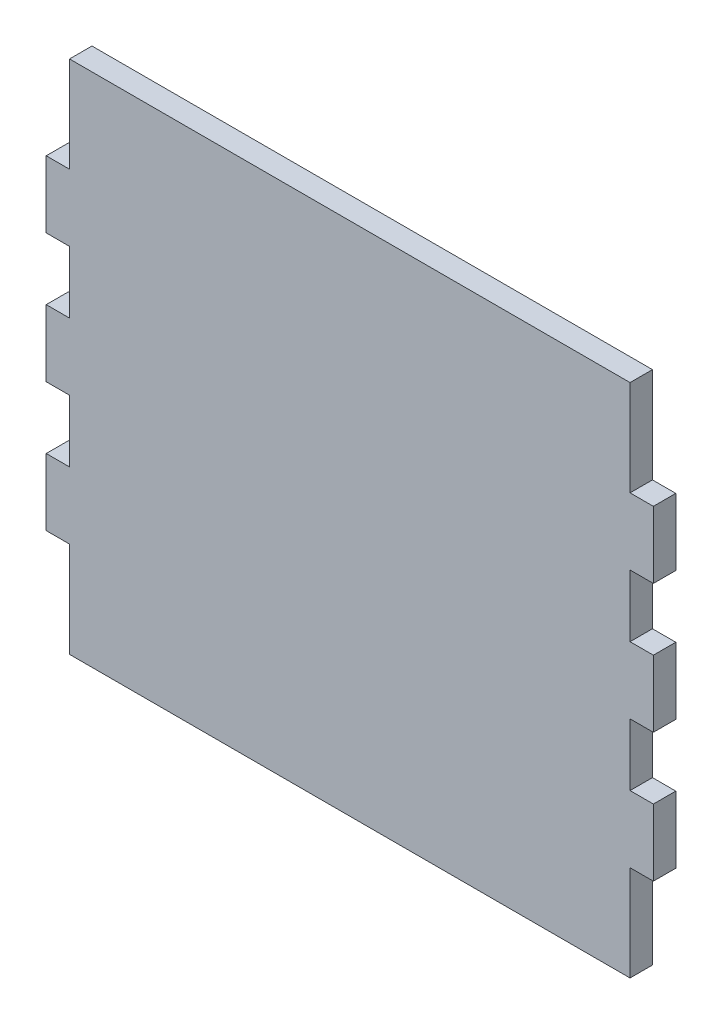
SolidWorks part; units mm, degrees
ref_plane "Front Plane" through (0, 0, 0) normal (0, 0, 1) x (1, 0, 0)
ref_plane "Top Plane" through (0, 0, 0) normal (0, 1, 0) x (1, 0, 0)
ref_plane "Right Plane" through (0, 0, 0) normal (1, 0, 0) x (0, 0, -1)
sketch "Sketch1" plane through (0, 0, 0) normal (0, 0, 1) x (1, 0, 0)
  line L0 (0, 0) -> (-85.979, 0) construction
  line L1 (79.375, 73.025) -> (-79.375, 73.025)
  line L2 (79.375, 73.025) -> (79.375, 45.974)
  line L3 (79.375, -73.025) -> (-79.375, -73.025)
  line L4 (-79.375, 73.025) -> (-79.375, 45.974)
  line L5 (79.375, 73.025) -> (-79.375, -73.025) construction
  line L6 (79.375, -73.025) -> (-79.375, 73.025) construction
  line L7 (-79.375, 9.4615) -> (-85.979, 9.4615)
  line L9 (-79.375, -9.4615) -> (-85.979, -9.4615)
  line L10 (-85.979, 9.4615) -> (-85.979, -9.4615)
  line L11 (-79.375, -27.051) -> (-85.979, -27.051)
  line L13 (-79.375, -45.974) -> (-85.979, -45.974)
  line L14 (-85.979, -27.051) -> (-85.979, -45.974)
  line L15 (-79.375, 45.974) -> (-85.979, 45.974)
  line L17 (-79.375, 27.051) -> (-85.979, 27.051)
  line L18 (-85.979, 45.974) -> (-85.979, 27.051)
  line L19 (-79.375, 73.025) -> (-79.375, 45.974) construction
  line L20 (-85.979, 36.5125) -> (0, 36.5125) construction
  line L21 (-85.979, -36.5125) -> (0, -36.5125) construction
  line L22 (-42.9895, -36.5125) -> (-42.9895, 0) construction
  line L23 (-42.9895, -36.5125) -> (-42.9895, -73.025) construction
  line L24 (-79.375, 27.051) -> (-79.375, 9.4615)
  line L25 (-79.375, -9.4615) -> (-79.375, -27.051)
  line L26 (-79.375, -45.974) -> (-79.375, -73.025)
  line L27 (0, 73.025) -> (0, -73.025) construction
  line L28 (85.979, -45.974) -> (85.979, -68.2942) construction
  line L29 (85.979, -9.4615) -> (85.979, -27.051) construction
  line L30 (85.979, 27.051) -> (85.979, 9.4615) construction
  line L31 (85.979, 68.2943) -> (85.979, 45.974) construction
  line L32 (79.375, 73.025) -> (79.375, 45.974) construction
  line L33 (79.375, -45.974) -> (79.375, -73.025)
  line L34 (79.375, -9.4615) -> (79.375, -27.051)
  line L35 (79.375, 27.051) -> (79.375, 9.4615)
  line L36 (85.979, 45.974) -> (85.979, 27.051)
  line L37 (79.375, 27.051) -> (85.979, 27.051)
  line L38 (79.375, 45.974) -> (85.979, 45.974)
  line L39 (85.979, -27.051) -> (85.979, -45.974)
  line L40 (79.375, -45.974) -> (85.979, -45.974)
  line L41 (79.375, -27.051) -> (85.979, -27.051)
  line L42 (85.979, 9.4615) -> (85.979, -9.4615)
  line L43 (79.375, -9.4615) -> (85.979, -9.4615)
  line L44 (79.375, 9.4615) -> (85.979, 9.4615)
  line L45 (-42.9895, 73.025) -> (-42.9895, 36.5125) construction
  line L46 (-42.9895, 36.5125) -> (-42.9895, 0) construction
  point P0 (0, 0)
  dimension "D1" = 158.75
  dimension "D2" = 146.05
  dimension "D3" = 18.923
  dimension "D4" = 6.604
extrude "Boss-Extrude1" add sketch "Sketch1" along normal mid plane 6.35
